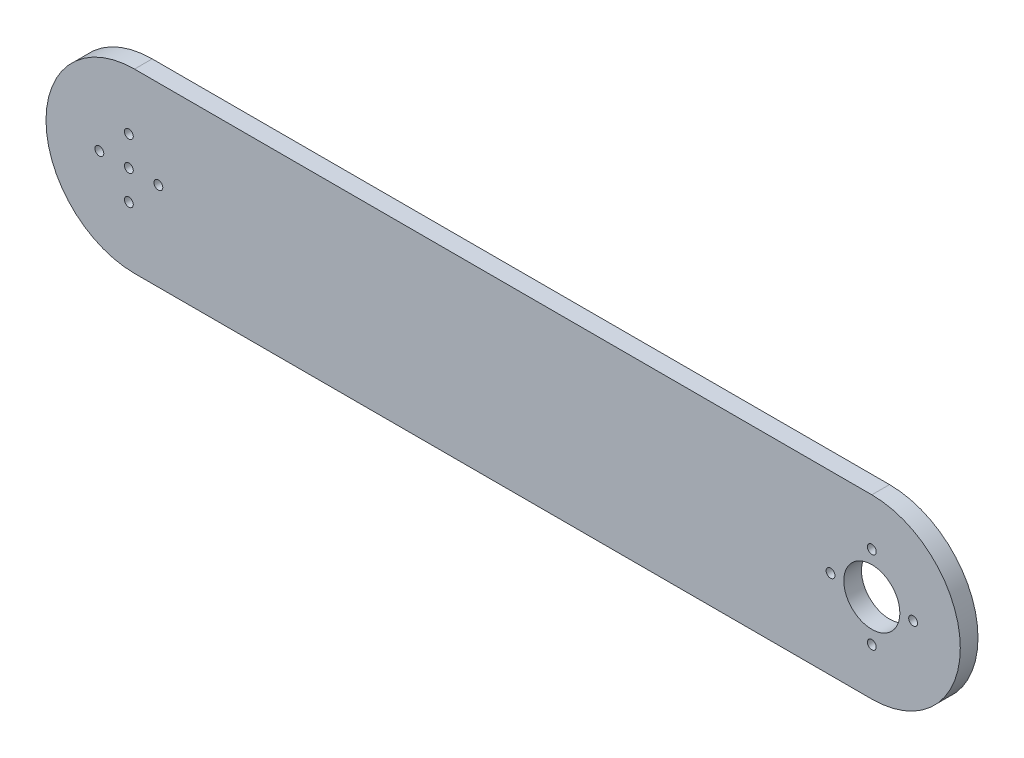
SolidWorks part; units mm, degrees
material "Aleación 1060"
ref_plane "Alzado" through (0, 0, 0) normal (0, 0, 1) x (1, 0, 0)
ref_plane "Planta" through (0, 0, 0) normal (0, 1, 0) x (1, 0, 0)
ref_plane "Vista lateral" through (0, 0, 0) normal (1, 0, 0) x (0, 0, -1)
sketch "Croquis1" plane through (0, 0, 0) normal (0, 0, 1) x (1, 0, 0)
  line L0 (400, 60) -> (370, 60) construction
  line L1 (120, 0) -> (370, 0)
  line L3 (120, 60) -> (370, 60)
  arc A0 (370, 60) -> (370, 0) centre (370, 30) cw
  arc A3 (120, 60) -> (120, 0) centre (120, 30) ccw
  point P10 (0, 0)
  point P13 (0, 60)
  dimension "D4" = 30
  dimension "D1" = 30
  dimension "D2" = 250
  dimension "D3" = 30
extrude "Saliente-Extruir1" add sketch "Croquis1" along normal blind 6
sketch "Croquis2" plane through (0, 0, 6) normal (0, 0, 1) x (1, 0, 0)
  line L0 (370, 60) -> (370, 0) construction
  circle A0 centre (370, 30) radius 9.5
  dimension "D1" = 19
extrude "Cortar-Extruir4" cut sketch "Croquis2" against normal blind 220
sketch "Croquis7" plane through (0, 0, 6) normal (0, 0, 1) x (1, 0, 0)
  line L0 (370, 49.5) -> (370, 10.5) construction
  circle A1 centre (370, 16) radius 1.5
  circle A2 centre (384, 30) radius 1.5
  circle A3 centre (356, 30) radius 1.5
  circle A4 centre (370, 44) radius 1.5
  point P0 (370, 30)
  dimension "D1" = 3
  dimension "D5" = 39
  dimension "D6" = 14
  dimension "D7" = 14
  dimension "D8" = 14
  dimension "D9" = 14
extrude "Cortar-Extruir5" cut sketch "Croquis7" against normal blind 6
sketch "Croquis8" plane through (0, 0, 0) normal (0, 0, -1) x (-1, 0, 0)
  line L0 (-370, 30) -> (-150, 30) construction
  line L1 (-150, 60) -> (-150, 0) construction
  line L3 (-370, 60) -> (-120, 60) construction
  line L4 (-120, 0) -> (-370, 0) construction
  line L6 (-134.0941, 0) -> (-134.0941, 60) construction
  line L8 (-134.0941, 30) -> (-90, 30) construction
  circle A0 centre (-150, 30) radius 3
  arc A1 (-120, 0) -> (-120, 60) centre (-120, 30) ccw construction
  circle A2 centre (-128.0941, 30) radius 2.85
  circle A3 centre (-118.0941, 30) radius 2.85
  circle A4 centre (-108.0941, 30) radius 2.85
  circle A5 centre (-118.0941, 40) radius 2.85
  circle A6 centre (-118.0941, 20) radius 2.85
  dimension "D2" = 6
  dimension "D4" = 5.7
  dimension "D5" = 6
  dimension "D1" = 220
  dimension "D3" = 15.9059
  dimension "D6" = 10
  dimension "D7" = 10
  dimension "D8" = 10
  dimension "D9" = 10
extrude "Cortar-Extruir6" cut sketch "Croquis8" against normal blind 0.3
ref_plane "Plano1" through (0, 0, 1.86) normal (0, 0, -1) x (-1, 0, 0)
sketch "Croquis9" plane through (0, 0, 1.86) normal (0, 0, -1) x (-1, 0, 0)
  circle A0 centre (-118.0941, 20) radius 1.5
  circle A1 centre (-108.0941, 30) radius 1.5
  circle A2 centre (-118.0941, 30) radius 1.5
  circle A3 centre (-128.0941, 30) radius 1.5
  circle A4 centre (-118.0941, 40) radius 1.5
  dimension "D1" = 3
loft "Cortar-Recubrir1" cut section edge at (125.2441, 30, 0) section "Croquis9" connector at (126.7321, 32.5035, 0) connector at (128.4763, 31.4505, 1.86)
loft "Cortar-Recubrir2" cut section edge at (115.2441, 30, 0.3) section "Croquis9<3>" connector at (116.8242, 32.5515, 0.3) connector at (119.3504, 30.8196, 1.86)
sketch "Croquis9<3>" plane through (0, 0, 1.86) normal (0, 0, -1) x (-1, 0, 0) same geometry as "Croquis9"
loft "Cortar-Recubrir3" cut section edge at (115.2441, 40, 0) section "Croquis9<4>" connector at (116.7811, 42.5295, 0) connector at (117.4274, 41.3437, 1.86)
sketch "Croquis9<4>" plane through (0, 0, 1.86) normal (0, 0, -1) x (-1, 0, 0) same geometry as "Croquis9"
loft "Cortar-Recubrir4" cut section face at (105.2441, 30, 0.3) section "Croquis9<5>" connector at (106.9295, 32.6012, 0.3) connector at (108.9263, 31.248, 1.86)
sketch "Croquis9<5>" plane through (0, 0, 1.86) normal (0, 0, -1) x (-1, 0, 0) same geometry as "Croquis9"
loft "Cortar-Recubrir5" cut section edge at (115.2441, 20, 0.3) section "Croquis9<6>" connector at (116.8822, 22.5795, 0.3) connector at (117.2785, 21.2589, 1.86)
sketch "Croquis9<6>" plane through (0, 0, 1.86) normal (0, 0, -1) x (-1, 0, 0) same geometry as "Croquis9"
extrude "Cortar-Extruir7" cut sketch "Croquis9<7>" against normal through all
sketch "Croquis9<7>" plane through (0, 0, 1.86) normal (0, 0, -1) x (-1, 0, 0) same geometry as "Croquis9"
